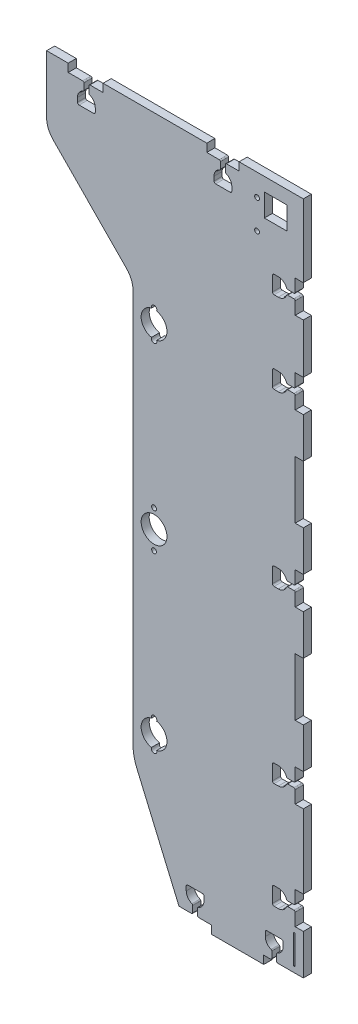
SolidWorks part; units mm, degrees
material "Beech"
ref_plane "Front Plane" through (0, 0, 0) normal (0, 0, 1) x (1, 0, 0)
ref_plane "Top Plane" through (0, 0, 0) normal (0, 1, 0) x (1, 0, 0)
ref_plane "Right Plane" through (0, 0, 0) normal (1, 0, 0) x (0, 0, -1)
sketch "Model" plane through (0, 0, 0) normal (0, 0, 1) x (1, 0, 0)
  line L0 (64, -418.0003) -> (93.9212, -356.6529)
  line L1 (96.4513, -345.6936) -> (96.4513, -101.9688)
  line L2 (99.7935, -91.6825) -> (132.5623, -46.5801)
  line L3 (136, -36) -> (136, -5)
  line L4 (60.5001, -418.0003) -> (64, -418.0003)
  line L5 (0, -30.0001) -> (0, -45)
  line L6 (0, -30.0001) -> (5, -30.0001)
  line L7 (5, -30.0001) -> (5, -26.5002)
  line L8 (5, -26.5002) -> (5, -22.2501)
  line L9 (5.75, -21.5001) -> (9.6746, -21.5001)
  line L10 (15.5004, -25.4999) -> (18.1001, -25.4999)
  line L11 (19.1001, -24.4999) -> (19.1001, -15.5001)
  line L12 (18.1001, -14.5001) -> (15.5004, -14.5001)
  line L13 (9.6751, -18.4989) -> (5.7502, -18.5)
  line L14 (5, -17.75) -> (5, 0)
  line L15 (5, 0) -> (54, 0)
  line L16 (126, -5) -> (126, 0)
  line L17 (126, 0) -> (136, 0)
  line L18 (136, 0) -> (136, -5)
  line L19 (54, 0) -> (54, -5)
  line L20 (54, -5) -> (61.7504, -5)
  line L21 (62.5004, -5.75) -> (62.4998, -9.6746)
  line L22 (58.5, -15.5004) -> (58.5, -18.1001)
  line L23 (59.5, -19.1001) -> (68.4998, -19.1001)
  line L24 (69.4998, -18.1001) -> (69.4998, -15.5004)
  line L25 (65.501, -9.6751) -> (65.5002, -5.7502)
  line L26 (66.2502, -5) -> (74, -5)
  line L27 (74, -5) -> (74, 0)
  line L28 (74, 0) -> (106, 0)
  line L29 (106, 0) -> (106, -5)
  line L30 (106, -5) -> (113.7504, -5)
  line L31 (114.5004, -5.75) -> (114.5103, -9.6746)
  line L32 (110.5106, -15.5004) -> (110.5106, -18.1001)
  line L33 (111.5106, -19.1001) -> (120.5104, -19.1001)
  line L34 (121.5104, -18.1001) -> (121.5104, -15.5004)
  line L35 (117.5115, -9.6751) -> (117.4916, -5.7502)
  line L36 (118.2416, -5) -> (126, -5)
  line L37 (83.5446, -211.9899) -> (83.5446, -234.9899) construction
  line L38 (83.5446, -105.0047) -> (83.5446, -121.9752) construction
  line L39 (83.5446, -223.4899) -> (453.5446, -223.4899) construction
  line L40 (83.5446, -341.9752) -> (83.5446, -325.0047) construction
  line L41 (268.5446, -223.4899) -> (268.5446, -128.9271) construction
  line L43 (60.5001, -418.0003) -> (56.25, -418.0003)
  line L44 (55.5002, -417.2501) -> (55.5002, -413.3256)
  line L45 (59.5, -407.4997) -> (59.5, -404.9)
  line L46 (58.5, -403.9) -> (49.5002, -403.9)
  line L47 (48.5002, -404.9) -> (48.5002, -407.4997)
  line L48 (52.499, -413.3251) -> (52.4997, -417.25)
  line L49 (51.7498, -418.0003) -> (44, -418.0003)
  line L50 (44, -418.0003) -> (44, -423.0003)
  line L51 (44, -423.0003) -> (30, -423.0003)
  line L52 (30, -423.0003) -> (30, -418.0003)
  line L53 (30, -418.0003) -> (22.2496, -418.0003)
  line L54 (21.4997, -417.2501) -> (21.4998, -413.3256)
  line L55 (25.4996, -407.4997) -> (25.4996, -404.9)
  line L56 (24.4996, -403.9) -> (15.4997, -403.9)
  line L57 (14.4997, -404.9) -> (14.4997, -407.4997)
  line L58 (18.4986, -413.3251) -> (18.4992, -417.25)
  line L59 (17.7494, -418.0003) -> (0, -418.0003)
  line L60 (0, -418.0003) -> (0, -393.0003)
  line L61 (0, -393.0003) -> (5, -393.0003)
  line L62 (5, -393.0003) -> (5, -385.2499)
  line L63 (5.7513, -384.5012) -> (9.6758, -384.499)
  line L64 (15.5017, -388.4988) -> (18.1014, -388.4988)
  line L65 (19.1001, -387.4976) -> (19.1001, -378.4977)
  line L66 (18.0989, -377.499) -> (15.4992, -377.499)
  line L67 (9.6751, -381.4996) -> (5.7502, -381.5)
  line L68 (5, -380.75) -> (5, -373.0002)
  line L69 (5, -373.0002) -> (0, -373.0002)
  line L70 (0, -373.0002) -> (0, -327.2502)
  line L71 (0, -327.2502) -> (5, -327.2502)
  line L72 (5, -327.2502) -> (5, -319.4997)
  line L73 (5.75, -318.7497) -> (9.6746, -318.7496)
  line L74 (15.5003, -322.7497) -> (18.0999, -322.7497)
  line L75 (19.1001, -321.7499) -> (19.1001, -312.75)
  line L76 (18.0997, -311.7505) -> (15.5, -311.7505)
  line L77 (9.6746, -315.7493) -> (5.7498, -315.7502)
  line L78 (5, -314.9997) -> (5, -307.2499)
  line L79 (5, -307.2499) -> (0, -307.2499)
  line L80 (0, -307.2499) -> (0, -282.2499)
  line L81 (0, -282.2499) -> (5, -282.2499)
  line L82 (5, -282.2499) -> (5, -246.4999)
  line L83 (5, -246.4999) -> (0, -246.4999)
  line L84 (0, -246.4999) -> (0, -221.4999)
  line L85 (0, -221.4999) -> (5, -221.4999)
  line L86 (5, -221.4999) -> (5, -213.7495)
  line L87 (5.75, -212.9995) -> (9.6746, -213.0004)
  line L88 (15.5002, -217.0006) -> (18.0999, -217.0006)
  line L89 (19.1001, -216.0009) -> (19.1001, -207.001)
  line L90 (18.1006, -206.0006) -> (15.5009, -206.0006)
  line L91 (9.6755, -209.9995) -> (5.7506, -209.9993)
  line L92 (5, -209.2497) -> (5, -201.4999)
  line L93 (5, -201.4999) -> (0, -201.4999)
  line L94 (0, -201.4999) -> (0, -176.4999)
  line L95 (0, -176.4999) -> (5, -176.4999)
  line L96 (5, -176.4999) -> (5, -140.7499)
  line L97 (5, -140.7499) -> (0, -140.7499)
  line L98 (0, -140.7499) -> (0, -115.7499)
  line L99 (0, -115.7499) -> (5, -115.7499)
  line L100 (5, -115.7499) -> (5, -107.9995)
  line L101 (5.75, -107.2495) -> (9.6746, -107.2502)
  line L102 (15.5003, -111.2502) -> (18.1, -111.2502)
  line L103 (19.1001, -110.2504) -> (19.1001, -101.2505)
  line L104 (18.1003, -100.2504) -> (15.5006, -100.2504)
  line L105 (9.6752, -104.2493) -> (5.7503, -104.2497)
  line L106 (5, -103.4998) -> (5, -95.75)
  line L107 (5, -95.75) -> (0, -95.75)
  line L108 (0, -95.75) -> (0, -70.75)
  line L109 (0, -70.75) -> (5, -70.75)
  line L110 (5, -70.75) -> (5, -45)
  line L111 (5, -45) -> (0, -45)
  line L112 (546, 0) -> (546, -45)
  line L113 (546, -45) -> (541, -45)
  line L114 (541, -45) -> (541, -52.75)
  line L115 (540.25, -53.5) -> (536.3254, -53.4999)
  line L116 (530.4996, -49.5001) -> (527.8999, -49.5001)
  line L117 (526.8994, -50.4997) -> (526.8994, -59.4995)
  line L118 (527.8994, -60.4995) -> (530.4991, -60.4995)
  line L119 (536.3245, -56.5007) -> (540.2494, -56.5006)
  line L120 (541, -57.2502) -> (541, -65)
  line L121 (541, -65) -> (546, -65)
  line L122 (546, -65) -> (546, -95.75)
  line L123 (546, -95.75) -> (541, -95.75)
  line L124 (541, -95.75) -> (541, -103.5)
  line L125 (540.25, -104.25) -> (536.3254, -104.2499)
  line L126 (530.4994, -100.2504) -> (527.8997, -100.2504)
  line L127 (526.8994, -101.2501) -> (526.8994, -110.2499)
  line L128 (527.8991, -111.2502) -> (530.4988, -111.2502)
  line L129 (536.3242, -107.2513) -> (540.2491, -107.2509)
  line L130 (541, -108.0002) -> (541, -115.75)
  line L131 (541, -115.75) -> (546, -115.75)
  line L132 (546, -115.75) -> (546, -140.7499)
  line L133 (546, -140.7499) -> (541, -140.7499)
  line L134 (541, -140.7499) -> (541, -176.4999)
  line L135 (541, -176.4999) -> (546, -176.4999)
  line L136 (546, -176.4999) -> (546, -201.4999)
  line L137 (546, -201.4999) -> (541, -201.4999)
  line L138 (541, -201.4999) -> (541, -209.2503)
  line L139 (540.25, -210.0003) -> (536.3254, -210.0004)
  line L140 (530.4995, -206.0006) -> (527.8999, -206.0006)
  line L141 (526.8994, -207.0002) -> (526.8994, -216)
  line L142 (527.8988, -217.0006) -> (530.4985, -217.0006)
  line L143 (536.3233, -213.0008) -> (540.2481, -213.0018)
  line L144 (541, -213.7501) -> (541, -221.4999)
  line L145 (541, -221.4999) -> (546, -221.4999)
  line L146 (546, -221.4999) -> (546, -246.4999)
  line L147 (546, -246.4999) -> (541, -246.4999)
  line L148 (541, -246.4999) -> (541, -282.2499)
  line L149 (541, -282.2499) -> (546, -282.2499)
  line L150 (546, -282.2499) -> (546, -307.2499)
  line L151 (546, -307.2499) -> (541, -307.2499)
  line L152 (541, -307.2499) -> (541, -315.0003)
  line L153 (540.25, -315.7503) -> (536.3254, -315.7505)
  line L154 (530.4997, -311.7505) -> (527.9, -311.7505)
  line L155 (526.8994, -312.7498) -> (526.8994, -321.7497)
  line L156 (527.8994, -322.7497) -> (530.4991, -322.7497)
  line L157 (536.3245, -318.751) -> (540.2494, -318.7508)
  line L158 (541, -319.5003) -> (541, -327.2502)
  line L159 (541, -327.2502) -> (546, -327.2502)
  line L160 (546, -327.2502) -> (546, -373.0002)
  line L161 (546, -373.0002) -> (541, -373.0002)
  line L162 (541, -373.0002) -> (541, -380.7506)
  line L163 (540.2494, -381.5) -> (536.3248, -381.4988)
  line L164 (530.4989, -377.499) -> (527.8993, -377.499)
  line L165 (526.8994, -378.4991) -> (526.8994, -387.499)
  line L166 (527.8996, -388.4988) -> (530.4993, -388.4988)
  line L167 (536.3249, -384.5008) -> (540.2498, -384.5005)
  line L168 (541, -385.2505) -> (541, -393.0003)
  line L169 (541, -393.0003) -> (546, -393.0003)
  line L170 (546, -393.0003) -> (546, -418.0003)
  line L171 (546, -418.0003) -> (530.2306, -418.0003)
  line L172 (529.4807, -417.2501) -> (529.4808, -413.3256)
  line L173 (533.4806, -407.4997) -> (533.4806, -404.9)
  line L174 (532.4806, -403.9) -> (523.4807, -403.9)
  line L175 (522.4807, -404.9) -> (522.4807, -407.4997)
  line L176 (526.4796, -413.3251) -> (526.4802, -417.25)
  line L177 (525.7304, -418.0003) -> (521.5, -418.0003)
  line L178 (506.2, 0) -> (546, 0)
  line L179 (535.88, -22.35) -> (521.88, -22.35)
  line L180 (521.88, -22.35) -> (521.88, -8.35)
  line L181 (521.88, -8.35) -> (535.88, -8.35)
  line L182 (535.88, -8.35) -> (535.88, -22.35)
  line L183 (498.4502, -5) -> (506.2, -5)
  line L184 (506.2, -5) -> (506.2, 0)
  line L185 (494.7, -5.75) -> (494.6999, -9.6746)
  line L186 (490.7001, -15.5004) -> (490.7001, -18.1001)
  line L187 (491.7001, -19.1001) -> (500.6999, -19.1001)
  line L188 (501.6999, -18.1001) -> (501.6999, -15.5004)
  line L189 (497.701, -9.6751) -> (497.7002, -5.7502)
  line L190 (469, -418.0003) -> (442.7881, -356.8435)
  line L191 (440.5239, -345.8131) -> (440.5239, -101.9214)
  line L192 (436.5094, -92.1087) -> (391.0145, -45.8127)
  line L193 (521.5, -418.0003) -> (521.5, -423.0003)
  line L194 (521.5, -423.0003) -> (489, -423.0003)
  line L195 (489, -423.0003) -> (489, -418.0003)
  line L196 (489, -418.0003) -> (481.2306, -418.0003)
  line L197 (480.4807, -417.2501) -> (480.4808, -413.3256)
  line L198 (484.4806, -407.4997) -> (484.4806, -404.9)
  line L199 (483.4806, -403.9) -> (474.4807, -403.9)
  line L200 (473.4807, -404.9) -> (473.4807, -407.4997)
  line L201 (477.4796, -413.3251) -> (477.4996, -417.2499)
  line L202 (476.7498, -418.0003) -> (469, -418.0003)
  line L209 (541, -396.5) -> (541, -414.5)
  line L210 (541, -414.5) -> (540, -414.5)
  line L211 (540, -414.5) -> (540, -396.5)
  line L212 (540, -396.5) -> (541, -396.5)
  line L213 (517.38, -10.4246) -> (520.13, -12.0123)
  line L214 (520.13, -12.0123) -> (520.13, -15.1877)
  line L215 (520.13, -15.1877) -> (517.38, -16.7754)
  line L216 (517.38, -16.7754) -> (514.63, -15.1877)
  line L217 (514.63, -15.1877) -> (514.63, -12.0123)
  line L218 (514.63, -12.0123) -> (517.38, -10.4246)
  line L219 (517.38, -28.4246) -> (520.13, -30.0123)
  line L220 (520.13, -30.0123) -> (520.13, -33.1878)
  line L221 (520.13, -33.1878) -> (517.38, -34.7755)
  line L222 (517.38, -34.7755) -> (514.63, -33.1878)
  line L223 (514.63, -33.1878) -> (514.63, -30.0123)
  line L224 (514.63, -30.0123) -> (517.38, -28.4246)
  line L225 (493.9655, -5) -> (486.2156, -5)
  line L226 (486.2156, -5) -> (486.2, -5)
  line L227 (486.2, -5) -> (486.2, 0)
  line L228 (486.2, 0) -> (421.975, 0)
  line L229 (421.975, 0) -> (421.975, -5)
  line L230 (421.975, -5) -> (413.87, -5)
  line L231 (413.12, -5.7502) -> (413.1208, -9.6751)
  line L232 (417.1197, -15.5004) -> (417.1197, -18.1001)
  line L233 (416.1197, -19.1001) -> (407.1199, -19.1001)
  line L234 (406.1199, -18.1001) -> (406.1199, -15.5004)
  line L235 (410.1196, -9.6746) -> (410.1198, -5.75)
  line L236 (409.3698, -5) -> (400.375, -5)
  line L237 (400.375, -5) -> (400.375, 0)
  line L238 (400.375, 0) -> (387, 0)
  line L239 (387, 0) -> (387, -36)
  line L240 (0, -30.0001) -> (0, 0) construction
  line L241 (0, 0) -> (5, 0) construction
  arc A0 (451.9455, -341.3285) -> (455.1438, -341.3285) centre (453.5446, -341.9752) ccw
  arc A1 (81.9455, -105.6514) -> (81.9455, -121.3285) centre (83.5446, -113.4899) ccw
  arc A2 (85.1438, -105.6514) -> (81.9455, -105.6514) centre (83.5446, -105.0047) ccw
  arc A3 (81.9455, -121.3285) -> (85.1438, -121.3285) centre (83.5446, -121.9752) ccw
  circle A4 centre (83.5446, -223.4899) radius 8
  circle A5 centre (83.5446, -211.9899) radius 1.5
  arc A6 (85.1438, -121.3285) -> (85.1438, -105.6514) centre (83.5446, -113.4899) ccw
  circle A7 centre (83.5446, -234.9899) radius 1.5
  arc A8 (96.4513, -345.6936) -> (93.9212, -356.6529) centre (71.4513, -345.6936) cw
  arc A9 (99.7935, -91.6825) -> (96.4513, -101.9688) centre (113.9513, -101.9688) ccw
  arc A10 (136, -36) -> (132.5623, -46.5801) centre (118, -36) cw
  arc A11 (387, -36) -> (391.0145, -45.8127) centre (401, -36) ccw
  arc A12 (436.5094, -92.1087) -> (440.5239, -101.9214) centre (426.5239, -101.9214) cw
  arc A13 (440.5239, -345.8131) -> (442.7881, -356.8435) centre (468.5239, -345.8131) ccw
  arc A14 (85.1438, -325.6514) -> (85.1438, -341.3285) centre (83.5446, -333.4899) cw
  arc A15 (81.9455, -325.6514) -> (85.1438, -325.6514) centre (83.5446, -325.0047) cw
  arc A16 (85.1438, -341.3285) -> (81.9455, -341.3285) centre (83.5446, -341.9752) cw
  arc A17 (81.9455, -341.3285) -> (81.9455, -325.6514) centre (83.5446, -333.4899) cw
  arc A18 (451.9455, -325.6514) -> (451.9455, -341.3285) centre (453.5446, -333.4899) ccw
  arc A19 (455.1438, -325.6514) -> (451.9455, -325.6514) centre (453.5446, -325.0047) ccw
  arc A20 (455.1438, -341.3285) -> (455.1438, -325.6514) centre (453.5446, -333.4899) ccw
  circle A21 centre (453.5446, -234.9899) radius 1.5
  circle A22 centre (453.5446, -223.4899) radius 8
  circle A23 centre (453.5446, -211.9899) radius 1.5
  arc A24 (455.1438, -121.3285) -> (451.9455, -121.3285) centre (453.5446, -121.9752) cw
  arc A25 (455.1438, -105.6514) -> (455.1438, -121.3285) centre (453.5446, -113.4899) cw
  arc A26 (451.9455, -121.3285) -> (451.9455, -105.6514) centre (453.5446, -113.4899) cw
  arc A27 (451.9455, -105.6514) -> (455.1438, -105.6514) centre (453.5446, -105.0047) cw
  circle A28 centre (517.38, -13.6) radius 1.5
  circle A29 centre (517.38, -13.6) radius 2.75 construction
  circle A30 centre (517.38, -31.6) radius 1.5
  circle A31 centre (517.38, -31.6) radius 2.75 construction
  spline S3 degree 3 poles (5, -22.2501) (5, -21.8359) (5.3358, -21.5001) (5.75, -21.5001) knots 3 3 3 3 4 4 4 4
  spline S4 degree 3 poles (9.6746, -21.5001) (9.9824, -21.5006) (10.2579, -21.6896) (10.3688, -21.9767) knots 5 5 5 5 6 6 6 6
  spline S5 degree 3 poles (10.3688, -21.9767) (11.1673, -24.033) (13.1709, -25.5004) (15.5004, -25.4999) knots 6 6 6 6 7 7 7 7
  spline S6 degree 3 poles (18.1001, -25.4999) (18.6524, -25.4999) (19.1001, -25.0522) (19.1001, -24.4999) knots 8 8 8 8 9 9 9 9
  spline S7 degree 3 poles (19.1001, -15.5001) (19.1001, -14.9478) (18.6524, -14.5001) (18.1001, -14.5001) knots 10 10 10 10 11 11 11 11
  spline S8 degree 3 poles (15.5004, -14.5001) (13.1712, -14.4996) (11.1678, -15.9666) (10.3691, -18.0225) knots 12 12 12 12 13 13 13 13
  spline S9 degree 3 poles (10.3691, -18.0225) (10.2582, -18.3095) (9.9828, -18.4984) (9.6751, -18.4989) knots 13 13 13 13 14 14 14 14
  spline S10 degree 3 poles (5.7502, -18.5) (5.3359, -18.5001) (5, -18.1643) (5, -17.75) knots 15 15 15 15 16 16 16 16
  spline S11 degree 3 poles (61.7504, -5) (62.1646, -5) (62.5004, -5.3358) (62.5004, -5.75) knots 2 2 2 2 3 3 3 3
  spline S12 degree 3 poles (62.4998, -9.6746) (62.4993, -9.9824) (62.3103, -10.2579) (62.0232, -10.3688) knots 4 4 4 4 5 5 5 5
  spline S13 degree 3 poles (62.0232, -10.3688) (59.9669, -11.1673) (58.4995, -13.1709) (58.5, -15.5004) knots 5 5 5 5 6 6 6 6
  spline S14 degree 3 poles (58.5, -18.1001) (58.5, -18.6524) (58.9477, -19.1001) (59.5, -19.1001) knots 7 7 7 7 8 8 8 8
  spline S15 degree 3 poles (68.4998, -19.1001) (69.0521, -19.1001) (69.4998, -18.6524) (69.4998, -18.1001) knots 9 9 9 9 10 10 10 10
  spline S16 degree 3 poles (69.4998, -15.5004) (69.5003, -13.1712) (68.0333, -11.1678) (65.9774, -10.3691) knots 11 11 11 11 12 12 12 12
  spline S17 degree 3 poles (65.9774, -10.3691) (65.6904, -10.2582) (65.5015, -9.9828) (65.501, -9.6751) knots 12 12 12 12 13 13 13 13
  spline S18 degree 3 poles (65.5002, -5.7502) (65.5001, -5.3359) (65.8359, -5) (66.2502, -5) knots 14 14 14 14 15 15 15 15
  spline S19 degree 3 poles (113.7504, -5) (114.1646, -5) (114.5004, -5.3358) (114.5004, -5.75) knots 20 20 20 20 21 21 21 21
  spline S20 degree 3 poles (114.5103, -9.6746) (114.5099, -9.9824) (114.3208, -10.2579) (114.0337, -10.3688) knots 22 22 22 22 23 23 23 23
  spline S21 degree 3 poles (114.0337, -10.3688) (111.9775, -11.1673) (110.5101, -13.1709) (110.5106, -15.5004) knots 23 23 23 23 24 24 24 24
  spline S22 degree 3 poles (110.5106, -18.1001) (110.5106, -18.6524) (110.9583, -19.1001) (111.5106, -19.1001) knots 25 25 25 25 26 26 26 26
  spline S23 degree 3 poles (120.5104, -19.1001) (121.0627, -19.1001) (121.5104, -18.6524) (121.5104, -18.1001) knots 27 27 27 27 28 28 28 28
  spline S24 degree 3 poles (121.5104, -15.5004) (121.5109, -13.1712) (120.0438, -11.1678) (117.988, -10.3691) knots 29 29 29 29 30 30 30 30
  spline S25 degree 3 poles (117.988, -10.3691) (117.701, -10.2582) (117.512, -9.9828) (117.5115, -9.6751) knots 30 30 30 30 31 31 31 31
  spline S26 degree 3 poles (117.4916, -5.7502) (117.4915, -5.3359) (117.8273, -5) (118.2416, -5) knots 32 32 32 32 33 33 33 33
  spline S57 degree 3 poles (56.25, -418.0003) (55.8358, -418.0002) (55.5001, -417.6644) (55.5002, -417.2501) knots 1 1 1 1 2 2 2 2
  spline S58 degree 3 poles (55.5002, -413.3256) (55.5007, -413.0178) (55.6897, -412.7423) (55.9768, -412.6314) knots 3 3 3 3 4 4 4 4
  spline S59 degree 3 poles (55.9768, -412.6314) (58.0331, -411.8329) (59.5005, -409.8292) (59.5, -407.4997) knots 4 4 4 4 5 5 5 5
  spline S60 degree 3 poles (59.5, -404.9) (59.5, -404.3477) (59.0523, -403.9) (58.5, -403.9) knots 6 6 6 6 7 7 7 7
  spline S61 degree 3 poles (49.5002, -403.9) (48.9479, -403.9) (48.5002, -404.3477) (48.5002, -404.9) knots 8 8 8 8 9 9 9 9
  spline S62 degree 3 poles (48.5002, -407.4997) (48.4997, -409.8289) (49.9667, -411.8324) (52.0226, -412.631) knots 10 10 10 10 11 11 11 11
  spline S63 degree 3 poles (52.0226, -412.631) (52.3096, -412.742) (52.4985, -413.0174) (52.499, -413.3251) knots 11 11 11 11 12 12 12 12
  spline S64 degree 3 poles (52.4997, -417.25) (52.4998, -417.6643) (52.1641, -418.0002) (51.7498, -418.0003) knots 13 13 13 13 14 14 14 14
  spline S65 degree 3 poles (22.2496, -418.0003) (21.8354, -418.0002) (21.4996, -417.6644) (21.4997, -417.2501) knots 19 19 19 19 20 20 20 20
  spline S66 degree 3 poles (21.4998, -413.3256) (21.5002, -413.0178) (21.6893, -412.7423) (21.9764, -412.6314) knots 21 21 21 21 22 22 22 22
  spline S67 degree 3 poles (21.9764, -412.6314) (24.0327, -411.8329) (25.5, -409.8292) (25.4996, -407.4997) knots 22 22 22 22 23 23 23 23
  spline S68 degree 3 poles (25.4996, -404.9) (25.4996, -404.3477) (25.0518, -403.9) (24.4996, -403.9) knots 24 24 24 24 25 25 25 25
  spline S69 degree 3 poles (15.4997, -403.9) (14.9474, -403.9) (14.4997, -404.3477) (14.4997, -404.9) knots 26 26 26 26 27 27 27 27
  spline S70 degree 3 poles (14.4997, -407.4997) (14.4993, -409.8289) (15.9663, -411.8324) (18.0221, -412.631) knots 28 28 28 28 29 29 29 29
  spline S71 degree 3 poles (18.0221, -412.631) (18.3091, -412.742) (18.4981, -413.0174) (18.4986, -413.3251) knots 29 29 29 29 30 30 30 30
  spline S72 degree 3 poles (18.4992, -417.25) (18.4994, -417.6643) (18.1637, -418.0002) (17.7494, -418.0003) knots 31 31 31 31 32 32 32 32
  spline S73 degree 3 poles (5, -385.2499) (5.0007, -384.8357) (5.337, -384.5004) (5.7513, -384.5012) knots 36 36 36 36 37 37 37 37
  spline S74 degree 3 poles (9.6758, -384.499) (9.9836, -384.4995) (10.2591, -384.6885) (10.37, -384.9756) knots 38 38 38 38 39 39 39 39
  spline S75 degree 3 poles (10.37, -384.9756) (11.1685, -387.0319) (13.1722, -388.4993) (15.5017, -388.4988) knots 39 39 39 39 40 40 40 40
  spline S76 degree 3 poles (18.1014, -388.4988) (18.6537, -388.4981) (19.1008, -388.0498) (19.1001, -387.4976) knots 41 41 41 41 42 42 42 42
  spline S77 degree 3 poles (19.1001, -378.4977) (19.0994, -377.9454) (18.6512, -377.4983) (18.0989, -377.499) knots 43 43 43 43 44 44 44 44
  spline S78 degree 3 poles (15.4992, -377.499) (13.17, -377.4992) (11.167, -378.9669) (10.369, -381.023) knots 45 45 45 45 46 46 46 46
  spline S79 degree 3 poles (10.369, -381.023) (10.2581, -381.31) (9.9828, -381.499) (9.6751, -381.4996) knots 46 46 46 46 47 47 47 47
  spline S80 degree 3 poles (5.7502, -381.5) (5.3359, -381.5001) (5, -381.1643) (5, -380.75) knots 48 48 48 48 49 49 49 49
  spline S81 degree 3 poles (5, -319.4997) (5, -319.0855) (5.3358, -318.7497) (5.75, -318.7497) knots 54 54 54 54 55 55 55 55
  spline S82 degree 3 poles (9.6746, -318.7496) (9.9824, -318.7501) (10.2579, -318.9392) (10.3688, -319.2263) knots 56 56 56 56 57 57 57 57
  spline S83 degree 3 poles (10.3688, -319.2263) (11.1671, -321.2826) (13.1707, -322.7501) (15.5003, -322.7497) knots 57 57 57 57 58 58 58 58
  spline S84 degree 3 poles (18.0999, -322.7497) (18.6522, -322.7498) (19.1, -322.3022) (19.1001, -321.7499) knots 59 59 59 59 60 60 60 60
  spline S85 degree 3 poles (19.1001, -312.75) (19.0999, -312.1978) (18.652, -311.7502) (18.0997, -311.7505) knots 61 61 61 61 62 62 62 62
  spline S86 degree 3 poles (15.5, -311.7505) (13.1708, -311.75) (11.1674, -313.217) (10.3687, -315.2729) knots 63 63 63 63 64 64 64 64
  spline S87 degree 3 poles (10.3687, -315.2729) (10.2578, -315.5599) (9.9823, -315.7488) (9.6746, -315.7493) knots 64 64 64 64 65 65 65 65
  spline S88 degree 3 poles (5.7498, -315.7502) (5.3355, -315.75) (4.9998, -315.414) (5, -314.9997) knots 66 66 66 66 67 67 67 67
  spline S89 degree 3 poles (5, -213.7495) (5, -213.3353) (5.3358, -212.9995) (5.75, -212.9995) knots 76 76 76 76 77 77 77 77
  spline S90 degree 3 poles (9.6746, -213.0004) (9.9824, -213.0009) (10.2579, -213.19) (10.3688, -213.4771) knots 78 78 78 78 79 79 79 79
  spline S91 degree 3 poles (10.3688, -213.4771) (11.1671, -215.5334) (13.1706, -217.0009) (15.5002, -217.0006) knots 79 79 79 79 80 80 80 80
  spline S92 degree 3 poles (18.0999, -217.0006) (18.6521, -217.0008) (19.1, -216.5532) (19.1001, -216.0009) knots 81 81 81 81 82 82 82 82
  spline S93 degree 3 poles (19.1001, -207.001) (19.1004, -206.4488) (18.6528, -206.0008) (18.1006, -206.0006) knots 83 83 83 83 84 84 84 84
  spline S94 degree 3 poles (15.5009, -206.0006) (13.1716, -206.0002) (11.1682, -207.4672) (10.3696, -209.523) knots 85 85 85 85 86 86 86 86
  spline S95 degree 3 poles (10.3696, -209.523) (10.2586, -209.81) (9.9832, -209.999) (9.6755, -209.9995) knots 86 86 86 86 87 87 87 87
  spline S96 degree 3 poles (5.7506, -209.9993) (5.3363, -209.9996) (5.0002, -209.664) (5, -209.2497) knots 88 88 88 88 89 89 89 89
  spline S97 degree 3 poles (5, -107.9995) (5, -107.5853) (5.3358, -107.2495) (5.75, -107.2495) knots 98 98 98 98 99 99 99 99
  spline S98 degree 3 poles (9.6746, -107.2502) (9.9824, -107.2507) (10.2579, -107.4397) (10.3688, -107.7269) knots 100 100 100 100 101 101 101 101
  spline S99 degree 3 poles (10.3688, -107.7269) (11.1672, -109.7831) (13.1708, -111.2506) (15.5003, -111.2502) knots 101 101 101 101 102 102 102 102
  spline S100 degree 3 poles (18.1, -111.2502) (18.6523, -111.2503) (19.1, -110.8027) (19.1001, -110.2504) knots 103 103 103 103 104 104 104 104
  spline S101 degree 3 poles (19.1001, -101.2505) (19.1002, -100.6982) (18.6526, -100.2505) (18.1003, -100.2504) knots 105 105 105 105 106 106 106 106
  spline S102 degree 3 poles (15.5006, -100.2504) (13.1714, -100.2499) (11.1679, -101.7169) (10.3693, -103.7728) knots 107 107 107 107 108 108 108 108
  spline S103 degree 3 poles (10.3693, -103.7728) (10.2584, -104.0598) (9.9829, -104.2487) (9.6752, -104.2493) knots 108 108 108 108 109 109 109 109
  spline S104 degree 3 poles (5.7503, -104.2497) (5.3361, -104.2498) (5.0001, -103.9141) (5, -103.4998) knots 110 110 110 110 111 111 111 111
  spline S105 degree 3 poles (541, -52.75) (541, -53.1642) (540.6642, -53.5) (540.25, -53.5) knots 3 3 3 3 4 4 4 4
  spline S106 degree 3 poles (536.3254, -53.4999) (536.0176, -53.4995) (535.7421, -53.3104) (535.6312, -53.0233) knots 5 5 5 5 6 6 6 6
  spline S107 degree 3 poles (535.6312, -53.0233) (534.8327, -50.967) (532.8291, -49.4997) (530.4996, -49.5001) knots 6 6 6 6 7 7 7 7
  spline S108 degree 3 poles (527.8999, -49.5001) (527.3476, -49.4999) (526.8997, -49.9474) (526.8994, -50.4997) knots 8 8 8 8 9 9 9 9
  spline S109 degree 3 poles (526.8994, -59.4995) (526.8994, -60.0518) (527.3471, -60.4995) (527.8994, -60.4995) knots 10 10 10 10 11 11 11 11
  spline S110 degree 3 poles (530.4991, -60.4995) (532.8283, -60.5) (534.8318, -59.033) (535.6304, -56.9771) knots 12 12 12 12 13 13 13 13
  spline S111 degree 3 poles (535.6304, -56.9771) (535.7414, -56.6901) (536.0168, -56.5012) (536.3245, -56.5007) knots 13 13 13 13 14 14 14 14
  spline S112 degree 3 poles (540.2494, -56.5006) (540.6637, -56.5003) (540.9998, -56.8359) (541, -57.2502) knots 15 15 15 15 16 16 16 16
  spline S113 degree 3 poles (541, -103.5) (541, -103.9142) (540.6642, -104.25) (540.25, -104.25) knots 21 21 21 21 22 22 22 22
  spline S114 degree 3 poles (536.3254, -104.2499) (536.0176, -104.2495) (535.7421, -104.0604) (535.6312, -103.7733) knots 23 23 23 23 24 24 24 24
  spline S115 degree 3 poles (535.6312, -103.7733) (534.8326, -101.7171) (532.8289, -100.2498) (530.4994, -100.2504) knots 24 24 24 24 25 25 25 25
  spline S116 degree 3 poles (527.8997, -100.2504) (527.3474, -100.2502) (526.8996, -100.6978) (526.8994, -101.2501) knots 26 26 26 26 27 27 27 27
  spline S117 degree 3 poles (526.8994, -110.2499) (526.8993, -110.8022) (527.3468, -111.25) (527.8991, -111.2502) knots 28 28 28 28 29 29 29 29
  spline S118 degree 3 poles (530.4988, -111.2502) (532.828, -111.2507) (534.8315, -109.7836) (535.6301, -107.7278) knots 30 30 30 30 31 31 31 31
  spline S119 degree 3 poles (535.6301, -107.7278) (535.7411, -107.4408) (536.0165, -107.2519) (536.3242, -107.2513) knots 31 31 31 31 32 32 32 32
  spline S120 degree 3 poles (540.2491, -107.2509) (540.6634, -107.2504) (540.9996, -107.5859) (541, -108.0002) knots 33 33 33 33 34 34 34 34
  spline S121 degree 3 poles (541, -209.2503) (541, -209.6646) (540.6642, -210.0004) (540.25, -210.0003) knots 43 43 43 43 44 44 44 44
  spline S122 degree 3 poles (536.3254, -210.0004) (536.0176, -210.0004) (535.7418, -209.8118) (535.6305, -209.5248) knots 45 45 45 45 46 46 46 46
  spline S123 degree 3 poles (535.6305, -209.5248) (534.8324, -207.4684) (532.8291, -206.0006) (530.4995, -206.0006) knots 46 46 46 46 47 47 47 47
  spline S124 degree 3 poles (527.8999, -206.0006) (527.3476, -206.0004) (526.8997, -206.4479) (526.8994, -207.0002) knots 48 48 48 48 49 49 49 49
  spline S125 degree 3 poles (526.8994, -216) (526.8991, -216.5523) (527.3465, -217.0003) (527.8988, -217.0006) knots 50 50 50 50 51 51 51 51
  spline S126 degree 3 poles (530.4985, -217.0006) (532.8277, -217.0007) (534.8309, -215.5334) (535.6293, -213.4774) knots 52 52 52 52 53 53 53 53
  spline S127 degree 3 poles (535.6293, -213.4774) (535.7402, -213.1904) (536.0156, -213.0014) (536.3233, -213.0008) knots 53 53 53 53 54 54 54 54
  spline S128 degree 3 poles (540.2481, -213.0018) (540.6624, -213.0008) (540.9991, -213.3358) (541, -213.7501) knots 55 55 55 55 56 56 56 56
  spline S129 degree 3 poles (541, -315.0003) (541, -315.4146) (540.6642, -315.7504) (540.25, -315.7503) knots 65 65 65 65 66 66 66 66
  spline S130 degree 3 poles (536.3254, -315.7505) (536.0176, -315.75) (535.7421, -315.5609) (535.6312, -315.2738) knots 67 67 67 67 68 68 68 68
  spline S131 degree 3 poles (535.6312, -315.2738) (534.8328, -313.2175) (532.8292, -311.7501) (530.4997, -311.7505) knots 68 68 68 68 69 69 69 69
  spline S132 degree 3 poles (527.9, -311.7505) (527.3478, -311.7501) (526.8998, -312.1976) (526.8994, -312.7498) knots 70 70 70 70 71 71 71 71
  spline S133 degree 3 poles (526.8994, -321.7497) (526.8994, -322.302) (527.3471, -322.7497) (527.8994, -322.7497) knots 72 72 72 72 73 73 73 73
  spline S134 degree 3 poles (530.4991, -322.7497) (532.8283, -322.7497) (534.8314, -321.2824) (535.6297, -319.2264) knots 74 74 74 74 75 75 75 75
  spline S135 degree 3 poles (535.6297, -319.2264) (535.7411, -318.9396) (536.0168, -318.751) (536.3245, -318.751) knots 75 75 75 75 76 76 76 76
  spline S136 degree 3 poles (540.2494, -318.7508) (540.6637, -318.7504) (540.9998, -319.0861) (541, -319.5003) knots 77 77 77 77 78 78 78 78
  spline S137 degree 3 poles (541, -380.7506) (540.9997, -381.1648) (540.6636, -381.5003) (540.2494, -381.5) knots 83 83 83 83 84 84 84 84
  spline S138 degree 3 poles (536.3248, -381.4988) (536.017, -381.4983) (535.7415, -381.3092) (535.6306, -381.0221) knots 85 85 85 85 86 86 86 86
  spline S139 degree 3 poles (535.6306, -381.0221) (534.8321, -378.9659) (532.8285, -377.4985) (530.4989, -377.499) knots 86 86 86 86 87 87 87 87
  spline S140 degree 3 poles (527.8993, -377.499) (527.347, -377.4991) (526.8993, -377.9468) (526.8994, -378.4991) knots 88 88 88 88 89 89 89 89
  spline S141 degree 3 poles (526.8994, -387.499) (526.8995, -388.0512) (527.3473, -388.4989) (527.8996, -388.4988) knots 90 90 90 90 91 91 91 91
  spline S142 degree 3 poles (530.4993, -388.4988) (532.8284, -388.4991) (534.8317, -387.0321) (535.6302, -384.9763) knots 92 92 92 92 93 93 93 93
  spline S143 degree 3 poles (535.6302, -384.9763) (535.7415, -384.6894) (536.0172, -384.5009) (536.3249, -384.5008) knots 93 93 93 93 94 94 94 94
  spline S144 degree 3 poles (540.2498, -384.5005) (540.6641, -384.5004) (541, -384.8362) (541, -385.2505) knots 95 95 95 95 96 96 96 96
  spline S145 degree 3 poles (530.2306, -418.0003) (529.8164, -418.0002) (529.4806, -417.6644) (529.4807, -417.2501) knots 100 100 100 100 101 101 101 101
  spline S146 degree 3 poles (529.4808, -413.3256) (529.4812, -413.0178) (529.6703, -412.7423) (529.9574, -412.6314) knots 102 102 102 102 103 103 103 103
  spline S147 degree 3 poles (529.9574, -412.6314) (532.0137, -411.8329) (533.481, -409.8292) (533.4806, -407.4997) knots 103 103 103 103 104 104 104 104
  spline S148 degree 3 poles (533.4806, -404.9) (533.4806, -404.3477) (533.0328, -403.9) (532.4806, -403.9) knots 105 105 105 105 106 106 106 106
  spline S149 degree 3 poles (523.4807, -403.9) (522.9284, -403.9) (522.4807, -404.3477) (522.4807, -404.9) knots 107 107 107 107 108 108 108 108
  spline S150 degree 3 poles (522.4807, -407.4997) (522.4803, -409.8289) (523.9473, -411.8324) (526.0031, -412.631) knots 109 109 109 109 110 110 110 110
  spline S151 degree 3 poles (526.0031, -412.631) (526.2901, -412.742) (526.4791, -413.0174) (526.4796, -413.3251) knots 110 110 110 110 111 111 111 111
  spline S152 degree 3 poles (526.4802, -417.25) (526.4804, -417.6643) (526.1447, -418.0002) (525.7304, -418.0003) knots 112 112 112 112 113 113 113 113
  spline S157 degree 3 poles (493.9655, -5) (494.3643, -5) (494.7001, -5.3358) (494.7, -5.75) knots 0 0 0 0 1 1 1 1
  spline S158 degree 3 poles (494.6999, -9.6746) (494.6994, -9.9824) (494.5103, -10.2579) (494.2232, -10.3688) knots 2 2 2 2 3 3 3 3
  spline S159 degree 3 poles (494.2232, -10.3688) (492.167, -11.1673) (490.6996, -13.1709) (490.7001, -15.5004) knots 3 3 3 3 4 4 4 4
  spline S160 degree 3 poles (490.7001, -18.1001) (490.7001, -18.6524) (491.1478, -19.1001) (491.7001, -19.1001) knots 5 5 5 5 6 6 6 6
  spline S161 degree 3 poles (500.6999, -19.1001) (501.2522, -19.1001) (501.6999, -18.6524) (501.6999, -18.1001) knots 7 7 7 7 8 8 8 8
  spline S162 degree 3 poles (501.6999, -15.5004) (501.7004, -13.1712) (500.2333, -11.1678) (498.1775, -10.3691) knots 9 9 9 9 10 10 10 10
  spline S163 degree 3 poles (498.1775, -10.3691) (497.8905, -10.2582) (497.7016, -9.9828) (497.701, -9.6751) knots 10 10 10 10 11 11 11 11
  spline S164 degree 3 poles (497.7002, -5.7502) (497.7001, -5.3359) (498.0359, -5) (498.4502, -5) knots 12 12 12 12 13 13 13 13
  spline S168 degree 3 poles (481.2306, -418.0003) (480.8164, -418.0002) (480.4806, -417.6644) (480.4807, -417.2501) knots 4 4 4 4 5 5 5 5
  spline S169 degree 3 poles (480.4808, -413.3256) (480.4812, -413.0178) (480.6703, -412.7423) (480.9574, -412.6314) knots 6 6 6 6 7 7 7 7
  spline S170 degree 3 poles (480.9574, -412.6314) (483.0137, -411.8329) (484.481, -409.8292) (484.4806, -407.4997) knots 7 7 7 7 8 8 8 8
  spline S171 degree 3 poles (484.4806, -404.9) (484.4806, -404.3477) (484.0328, -403.9) (483.4806, -403.9) knots 9 9 9 9 10 10 10 10
  spline S172 degree 3 poles (474.4807, -403.9) (473.9284, -403.9) (473.4807, -404.3477) (473.4807, -404.9) knots 11 11 11 11 12 12 12 12
  spline S173 degree 3 poles (473.4807, -407.4997) (473.4803, -409.8289) (474.9473, -411.8324) (477.0031, -412.631) knots 13 13 13 13 14 14 14 14
  spline S174 degree 3 poles (477.0031, -412.631) (477.2901, -412.742) (477.4791, -413.0174) (477.4796, -413.3251) knots 14 14 14 14 15 15 15 15
  spline S175 degree 3 poles (477.4996, -417.2499) (477.4998, -417.6642) (477.1641, -418.0002) (476.7498, -418.0003) knots 16 16 16 16 17 17 17 17
  spline S206 degree 3 poles (413.87, -5) (413.4558, -5) (413.1199, -5.3359) (413.12, -5.7502) knots 6 6 6 6 7 7 7 7
  spline S207 degree 3 poles (413.1208, -9.6751) (413.1213, -9.9828) (413.3103, -10.2582) (413.5973, -10.3691) knots 8 8 8 8 9 9 9 9
  spline S208 degree 3 poles (413.5973, -10.3691) (415.6531, -11.1678) (417.1202, -13.1712) (417.1197, -15.5004) knots 9 9 9 9 10 10 10 10
  spline S209 degree 3 poles (417.1197, -18.1001) (417.1197, -18.6524) (416.672, -19.1001) (416.1197, -19.1001) knots 11 11 11 11 12 12 12 12
  spline S210 degree 3 poles (407.1199, -19.1001) (406.5676, -19.1001) (406.1199, -18.6524) (406.1199, -18.1001) knots 13 13 13 13 14 14 14 14
  spline S211 degree 3 poles (406.1199, -15.5004) (406.1194, -13.1709) (407.5868, -11.1673) (409.643, -10.3688) knots 15 15 15 15 16 16 16 16
  spline S212 degree 3 poles (409.643, -10.3688) (409.9301, -10.2579) (410.1192, -9.9824) (410.1196, -9.6746) knots 16 16 16 16 17 17 17 17
  spline S213 degree 3 poles (410.1198, -5.75) (410.1198, -5.3358) (409.7841, -5) (409.3698, -5) knots 18 18 18 18 19 19 19 19
  dimension "D1" = 113.4899
  dimension "D7" = 16
  dimension "D8" = 3.45
  dimension "D10" = 16
  dimension "D11" = 3
  dimension "D12" = 3
  dimension "D27" = 25
  dimension "D32" = 17.5
  dimension "D34" = 18
  dimension "D47" = 14
  dimension "D48" = 14
  dimension "D57" = 28
  dimension "D58" = 370
  dimension "D59" = 14
  dimension "D64" = 3
  dimension "D66" = 3
  dimension "D67" = 18
  dimension "D2" = 110
  dimension "D3" = 23
  dimension "D4" = 78.5446
  dimension "D5" = 5
  dimension "D6" = 45
  dimension "D9" = 16.9706
  dimension "D13" = 25.75
  dimension "D14" = 25
  dimension "D15" = 19.9999
  dimension "D16" = 35.75
  dimension "D17" = 25
  dimension "D18" = 20
  dimension "D19" = 25
  dimension "D20" = 20.0002
  dimension "D21" = 20.0002
  dimension "D22" = 14
  dimension "D23" = 64
  dimension "D24" = 30
  dimension "D25" = 45.75
  dimension "D26" = 116
  dimension "D28" = 91.4513
  dimension "D29" = 36
  dimension "D30" = 36
  dimension "D31" = 136
  dimension "D33" = 49
  dimension "D35" = 20
  dimension "D36" = 32
  dimension "D37" = 20
  dimension "D38" = 546
  dimension "D39" = 39.8
  dimension "D40" = 20
  dimension "D41" = 64.225
  dimension "D42" = 21.6
  dimension "D43" = 154
  dimension "D44" = 45
  dimension "D45" = 44.5
  dimension "D46" = 105.4761
  dimension "D49" = 36
  dimension "D50" = 20
  dimension "D51" = 30.75
  dimension "D52" = 20
  dimension "D53" = 24.5
  dimension "D54" = 32.5
  dimension "D55" = 20
  dimension "D56" = 113.2
  dimension "D60" = 8.35
  dimension "D61" = 10.12
  dimension "D62" = 5.5
  dimension "D63" = 4.5
  dimension "D65" = 5.25
  dimension "D68" = 5.5
extrude "Boss-Extrude1" [suppressed] add sketch "Model" along normal blind 5 contours S104 L105 S103 S102 L104 S101 L103 S100 L102 S99 S98 L101 S97 L100 L99 L98 L97 L96 L95 L94 L93 L92 S96 L91 S95 S94 L90 S93 L89 S92 L88 S91 S90 L87 S89 L86 L85 L84 L83 L82 L81 L80 L79 L78 S88 L77 S87 S86 L76 S85 L75
extrude "Boss-Extrude2" add sketch "Model<3>" along normal blind 5 contours L235 S213 L236 L237 L238 L239 A11 L192 A12 L191 A13 L190 L202 S175 L201 S174 S173 L200 S172 L199 S171 L198 S170 S169 L197 S168 L196 L195 L194 L193 L177 S152 L176 S151 S150 L175 S149 L174 S148 L173 S147 S146 L172 S145 L171 L170 L169 L168 S144 L167 S143 | L218 L217 L216 L215 L214 L213 | L224 L223 L222 L221 L220 L219 region at (487.1575, -192.9076, 0) region at (518.713, -11.2912, 0) region at (518.713, -29.2912, 0)
sketch "Model<3>" plane through (0, 0, 0) normal (0, 0, 1) x (1, 0, 0) same geometry as "Model"
extrude "Cut-Extrude1" cut sketch "Model<4>" along normal blind 2 contours L218 L217 L216 L215 L214 L213 A28 | L224 L223 L222 L221 L220 L219 A30 region at (518.713, -11.2912, 0) region at (518.713, -29.2912, 0)
sketch "Model<4>" plane through (0, 0, 0) normal (0, 0, 1) x (1, 0, 0) same geometry as "Model"
